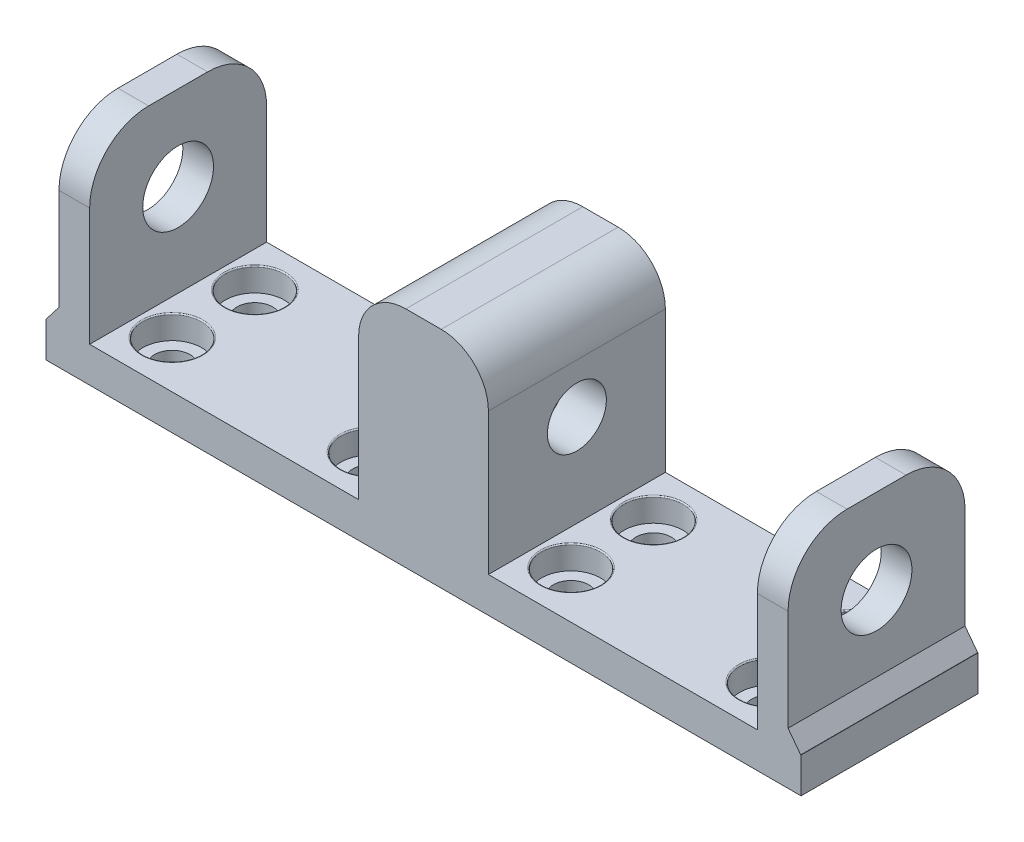
SolidWorks part; units mm, degrees
ref_plane "Alzado" through (0, 0, 0) normal (0, 0, 1) x (1, 0, 0)
ref_plane "Planta" through (0, 0, 0) normal (0, 1, 0) x (1, 0, 0)
ref_plane "Vista lateral" through (0, 0, 0) normal (1, 0, 0) x (0, 0, -1)
sketch "Croquis1" plane through (0, 0, 0) normal (0, 0, 1) x (1, 0, 0)
  line L0 (0, 9.5) -> (0, -9.5) construction
  line L1 (-1.5, 9.5) -> (1.5, 9.5)
  line L2 (-5.5, 5.5) -> (-5.5, -6.5)
  line L3 (-5.5, -9.5) -> (5.5, -9.5)
  line L4 (5.5, 5.5) -> (5.5, -6.5)
  line L5 (-5.5, 9.5) -> (5.5, -9.5) construction
  line L6 (-5.5, -9.5) -> (5.5, 9.5) construction
  line L7 (-5.5, -9.5) -> (-11.5, -9.5)
  line L9 (-5.5, -6.5) -> (-11.5, -6.5)
  line L10 (-11.5, -9.5) -> (-11.5, -6.5)
  line L11 (5.5, -6.5) -> (11.5, -6.5)
  line L12 (11.5, -9.5) -> (11.5, -6.5)
  line L13 (5.5, -9.5) -> (11.5, -9.5)
  arc A0 (5.5, 5.5) -> (1.5, 9.5) centre (1.5, 5.5) ccw
  arc A1 (-5.5, 5.5) -> (-1.5, 9.5) centre (-1.5, 5.5) cw
  point P0 (0, 0)
  dimension "D1" = 4
  dimension "D2" = 6
  dimension "D3" = 3
  dimension "D4" = 11
  dimension "D5" = 15
extrude "Saliente-Extruir1" add sketch "Croquis1" against normal blind 15
sketch "Croquis2" plane through (5.5, 0, 0) normal (1, 0, 0) x (0, 0, -1)
  line L0 (7.5, 9.5) -> (7.5, -6.5) construction
  line L1 (15, 9.5) -> (0, 9.5) construction
  line L2 (15, -6.5) -> (0, -6.5) construction
  line L3 (15, -9.5) -> (0, -9.5) construction
  circle A0 centre (7.5, 1.32) radius 2.5
  dimension "D2" = 5
  dimension "D1" = 10.82
extrude "Cortar-Extruir1" cut sketch "Croquis2" against normal blind 3.5
sketch "Croquis3" plane through (-5.5, 0, 0) normal (-1, 0, 0) x (0, 0, 1)
  line L0 (-7.5, 9.5) -> (-7.5, -6.5) construction
  line L1 (-15, 9.5) -> (0, 9.5) construction
  line L2 (-15, -6.5) -> (0, -6.5) construction
  line L3 (-15, -9.5) -> (0, -9.5) construction
  circle A0 centre (-7.5, 1.32) radius 2.5
  dimension "D2" = 5
  dimension "D1" = 10.82
extrude "Cortar-Extruir2" cut sketch "Croquis3" against normal blind 3.5
sketch "Croquis4" plane through (0, -6.5, 0) normal (0, 1, 0) x (1, 0, 0)
  line L0 (0, 15) -> (0, 0) construction
  line L1 (1.5, 15) -> (-1.5, 15) construction
  line L2 (-8.5, 15) -> (-8.5, 0) construction
  line L3 (-5.5, 15) -> (-11.5, 15) construction
  line L4 (-5.5, 0) -> (-11.5, 0) construction
  circle A0 centre (-8.5, 11) radius 2.5
  circle A1 centre (-8.5, 4) radius 2.5
  circle A2 centre (8.5, 4) radius 2.5
  circle A3 centre (8.5, 11) radius 2.5
  dimension "D1" = 5
  dimension "D2" = 4
  dimension "D3" = 4
extrude "Cortar-Extruir3" cut sketch "Croquis4" against normal blind 2
fillet "Redondeo1" radius 0.1 4 edges at (11, -6.5, -4) (11, -6.5, -11) (-11, -6.5, -4) (-11, -6.5, -11)
sketch "Croquis5" plane through (0, -6.5, 0) normal (0, 1, 0) x (1, 0, 0)
  line L0 (-8.5, 15) -> (-8.5, 0) construction
  line L1 (-5.5, 15) -> (-11.5, 15) construction
  line L2 (-5.5, 0) -> (-11.5, 0) construction
  line L3 (0, 15) -> (0, 0) construction
  line L4 (1.5, 15) -> (-1.5, 15) construction
  line L5 (1.5, 0) -> (-1.5, 0) construction
  circle A0 centre (-8.5, 11) radius 1.5
  circle A1 centre (-8.5, 4) radius 1.5
  circle A2 centre (-8.5, 11) radius 2.6 construction
  circle A3 centre (8.5, 4) radius 1.5
  circle A4 centre (8.5, 11) radius 1.5
  dimension "D1" = 3
extrude "Cortar-Extruir4" cut sketch "Croquis5" against normal through all
sketch "Croquis6" plane through (-11.5, 0, 0) normal (-1, 0, 0) x (0, 0, 1)
  line L1 (-15, -6.5) -> (0, -6.5)
  line L2 (-15, -6.5) -> (-15, -9.5)
  line L3 (-15, -9.5) -> (0, -9.5)
  line L4 (0, -6.5) -> (0, -9.5)
extrude "Saliente-Extruir2" add sketch "Croquis6" along normal blind 20.5
sketch "Croquis7" plane through (11.5, 0, 0) normal (1, 0, 0) x (0, 0, -1)
  line L1 (0, -6.5) -> (15, -6.5)
  line L2 (0, -6.5) -> (0, -9.5)
  line L3 (0, -9.5) -> (15, -9.5)
  line L4 (15, -6.5) -> (15, -9.5)
extrude "Saliente-Extruir3" add sketch "Croquis7" along normal blind 20.5
sketch "Croquis8" plane through (0, -6.5, 0) normal (0, 1, 0) x (1, 0, 0)
  line L0 (-5.5, 15) -> (-32, 15) construction
  line L1 (-30.9, 15) -> (-28.3, 15)
  line L2 (-30.9, 15) -> (-30.9, 0)
  line L3 (-30.9, 0) -> (-28.3, 0)
  line L4 (-28.3, 15) -> (-28.3, 0)
  line L5 (-5.5, 0) -> (-32, 0) construction
  line L6 (0, 15) -> (0, 0) construction
  line L7 (1.5, 15) -> (-1.5, 15) construction
  line L8 (30.9, 0) -> (28.3, 0)
  line L9 (28.3, 15) -> (28.3, 0)
  line L10 (30.9, 15) -> (28.3, 15)
  line L11 (30.9, 15) -> (30.9, 0)
  line L12 (-32, 0) -> (-32, 15) construction
  dimension "D1" = 2.6
  dimension "D2" = 1.1
extrude "Saliente-Extruir4" add sketch "Croquis8" along normal blind 15
fillet "Redondeo4" radius 5 2 edges at (-29.6, 8.5, -15) (-29.6, 8.5, 0)
fillet "Redondeo5" radius 5 2 edges at (29.6, 8.5, -15) (29.6, 8.5, 0)
ref_plane "Plano12" through (0, 0, -7.5) normal (0, 0, 1) x (1, 0, 0)
sketch "Croquis17" plane through (0, 0, -7.5) normal (0, 0, 1) x (1, 0, 0)
  line L0 (30.9, -5.0818) -> (31.9724, -6.5)
  line L1 (30.9, 3.5) -> (30.9, -6.5) construction
  line L3 (32, -6.5) -> (30.9, -6.5) construction
rib "Nervio1" sketch "Croquis17" sketch "Croquis17" thickness 15 extrusion direction parallel to sketch draft on no parameters "D1"=15
sketch "Croquis22" plane through (0, 0, -7.5) normal (0, 0, 1) x (1, 0, 0)
  line L0 (-31.9933, -6.5) -> (-30.9, -5.0818)
  line L1 (-30.9, -6.5) -> (-32, -6.5) construction
  line L2 (-30.9, 8.5) -> (-30.9, 3.5) construction
  line L4 (-30.9, 3.5) -> (-30.9, -6.5) construction
rib "Nervio2" sketch "Croquis22" sketch "Croquis22" thickness 15 extrusion direction parallel to sketch draft on no parameters "D1"=15
sketch "Croquis23" plane through (30.9, 0, 0) normal (1, 0, 0) x (0, 0, -1)
  line L0 (7.5, 8.5) -> (7.5, -5.0818) construction
  line L1 (5, 8.5) -> (10, 8.5) construction
  line L2 (0, -5.0818) -> (15, -5.0818) construction
  line L3 (0, -9.5) -> (15, -9.5) construction
  circle A0 centre (7.5, 1.32) radius 3
  dimension "D1" = 6
  dimension "D2" = 10.82
extrude "Cortar-Extruir5" cut sketch "Croquis23" against normal blind 7
sketch "Croquis24" plane through (-30.9, 0, 0) normal (-1, 0, 0) x (0, 0, 1)
  line L0 (-7.5, 8.5) -> (-7.5, -5.0818) construction
  line L1 (-10, 8.5) -> (-5, 8.5) construction
  line L2 (-15, -5.0818) -> (0, -5.0818) construction
  line L3 (-15, -9.5) -> (0, -9.5) construction
  circle A0 centre (-7.5, 1.32) radius 3
  dimension "D1" = 6
  dimension "D2" = 10.82
extrude "Cortar-Extruir6" cut sketch "Croquis24" against normal blind 7
sketch "Croquis27" plane through (0, -6.5, 0) normal (0, 1, 0) x (1, 0, 0)
  line L0 (-25.3, 15) -> (-25.3, 0) construction
  line L1 (-5.5, 15) -> (-28.3, 15) construction
  line L2 (-5.5, 0) -> (-28.3, 0) construction
  line L3 (-28.3, 0) -> (-28.3, 15) construction
  circle A0 centre (-25.3, 11) radius 1.5
  circle A1 centre (-25.3, 4) radius 1.5
  circle A2 centre (-25.3, 11) radius 2.5
  circle A3 centre (-25.3, 4) radius 2.5
  dimension "D1" = 3
  dimension "D2" = 5
  dimension "D3" = 4
  dimension "D4" = 4
  dimension "D5" = 3
extrude "Cortar-Extruir8" cut sketch "Croquis27" against normal through all contours A0 | A1
sketch "Croquis29" plane through (0, -6.5, 0) normal (0, 1, 0) x (1, 0, 0)
  circle A0 centre (-25.3, 11) radius 2.5
  circle A1 centre (-25.3, 4) radius 2.5
  dimension "D1" = 5
extrude "Cortar-Extruir9" cut sketch "Croquis29" against normal blind 2
fillet "Redondeo6" radius 0.1 2 edges at (-27.8, -6.5, -4) (-27.8, -6.5, -11)
sketch "Croquis30" plane through (0, -6.5, 0) normal (0, 1, 0) x (1, 0, 0)
  line L0 (25.3, 15) -> (25.3, 0) construction
  line L1 (28.3, 15) -> (5.5, 15) construction
  line L2 (28.3, 0) -> (5.5, 0) construction
  line L3 (28.3, 15) -> (28.3, 0) construction
  circle A0 centre (25.3, 11) radius 1.5
  circle A1 centre (25.3, 4) radius 1.5
  dimension "D2" = 3
  dimension "D1" = 3
  dimension "D3" = 4
  dimension "D4" = 4
extrude "Cortar-Extruir10" cut sketch "Croquis30" against normal through all
sketch "Croquis32" plane through (0, -6.5, 0) normal (0, 1, 0) x (1, 0, 0)
  circle A0 centre (25.3, 11) radius 2.5
  circle A1 centre (25.3, 4) radius 2.5
  dimension "D1" = 5
extrude "Cortar-Extruir11" cut sketch "Croquis32" against normal blind 2
fillet "Redondeo7" radius 0.1 2 edges at (22.8, -6.5, -4) (22.8, -6.5, -11)
